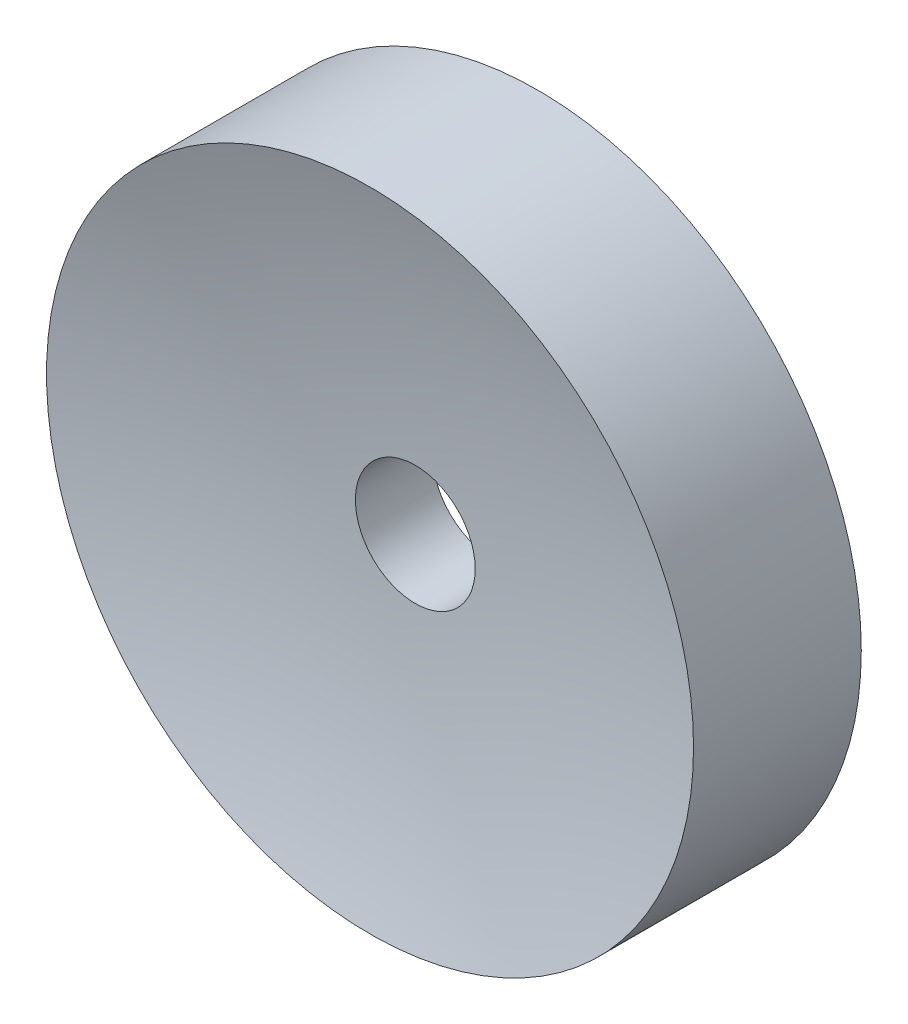
SolidWorks part; units mm, degrees
ref_plane "Front Plane" through (0, 0, 0) normal (0, 0, 1) x (1, 0, 0)
ref_plane "Top Plane" through (0, 0, 0) normal (0, 1, 0) x (1, 0, 0)
ref_plane "Right Plane" through (0, 0, 0) normal (1, 0, 0) x (0, 0, -1)
sketch "Sketch1" plane through (0, 0, 0) normal (0, 0, 1) x (1, 0, 0)
  line L0 (0, -6.75) -> (0, 6.75) construction
  circle A0 centre (0, 0) radius 1.25
  circle A1 centre (0, 0) radius 6.75
  point P7 (0, 0)
  dimension "D2" = 2.5
  dimension "D1" = 5.5
extrude "Boss-Extrude1" add sketch "Sketch1" along normal mid plane 3.5
sketch "Sketch2" plane through (0, 0, 0) normal (0, 1, 0) x (1, 0, 0)
  line L0 (-6.75, 1.75) -> (-6.75, -1.75) construction
  line L2 (-6.75, 1.75) -> (6.75, 1.75)
  line L3 (0, 3.9821) -> (0, -0.4821) construction
  arc A0 (6.75, 1.75) -> (-6.75, 1.75) centre (0, 24.576) cw
  point P9 (0, 1.75)
  dimension "D1" = 23.8031
ref_axis "Axis1" through (0, 0, 1.75) along (0, 0, -1)
revolve "Cut-Revolve1" cut sketch "Sketch2" angle 360 about L3 region at (-2.5383, 0, -1.3585)
mirror "Mirror1" about plane through (0, 0, 0) normal (0, 0, 1) of "Cut-Revolve1"
